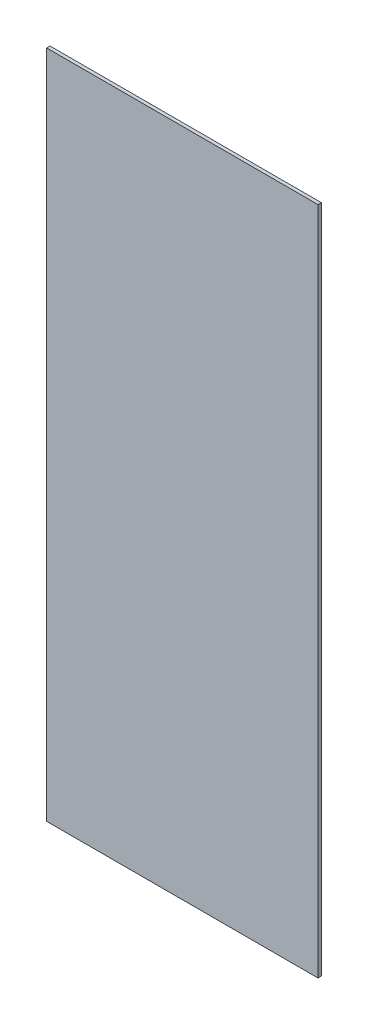
SolidWorks part; units mm, degrees
material "201 Annealed Stainless Steel (SS)"
ref_plane "Front Plane" through (0, 0, 0) normal (0, 0, 1) x (1, 0, 0)
ref_plane "Top Plane" through (0, 0, 0) normal (0, 1, 0) x (1, 0, 0)
ref_plane "Right Plane" through (0, 0, 0) normal (1, 0, 0) x (0, 0, -1)
sketch "Sketch1" plane through (0, 0, 0) normal (0, 0, 1) x (1, 0, 0)
  line L1 (-81, -200) -> (81, -200)
  line L2 (-81, -200) -> (-81, 200)
  line L3 (-81, 200) -> (81, 200)
  line L4 (81, -200) -> (81, 200)
  line L5 (-81, -200) -> (81, 200) construction
  line L6 (-81, 200) -> (81, -200) construction
  point P0 (0, 0)
  dimension "D1" = 162
  dimension "D2" = 400
extrude "Boss-Extrude1" add sketch "Sketch1" along normal blind 2
sketch "Sketch2" plane through (0, 0, 0) normal (0, 0, -1) x (-1, 0, 0)
  line L0 (79, 200) -> (79, -200) construction
  line L1 (-79, 314.7216) -> (-204.3993, 314.7216)
  line L2 (-79, 314.7216) -> (-79, -251.9618)
  line L3 (-79, -251.9618) -> (-204.3993, -251.9618)
  line L4 (-204.3993, 314.7216) -> (-204.3993, -251.9618)
  line L6 (79, 279.3211) -> (244.4765, 279.3211)
  line L7 (79, 279.3211) -> (79, -295.1839)
  line L8 (79, -295.1839) -> (244.4765, -295.1839)
  line L9 (244.4765, 279.3211) -> (244.4765, -295.1839)
  line L10 (-79, -200) -> (-79, -140) construction
  dimension "D1" = 158
extrude "Cut-Extrude1" [suppressed] cut sketch "Sketch2" against normal through all
sketch "Sketch3" [suppressed] plane through (0, 106, 0) normal (-1, 0, 0) x (0, 0, -1)
  line L0 (-2, -94) -> (0, -94) construction
  circle A0 centre (-7, -84) radius 2.5
  point P6 (-2, -94)
  dimension "D3" = 5
  dimension "D1" = 15
  dimension "D2" = 5
surface "Surface-Extrude1" [suppressed] sketch "Sketch3"
sketch "Sketch4" [suppressed] plane through (-81, 0, 0) normal (-1, 0, 0) x (0, 0, 1)
  line L1 (2, 200) -> (0, 200) construction
  line L2 (0, -200) -> (0, 200) construction
  point P0 (7.5, 196)
  dimension "D1" = 4
  dimension "D2" = 7.5
ref_axis "Axis1" [suppressed] through (-81, 196, 7.5) along (1, 0, 0)
sketch "Sketch5" [suppressed] plane through (0, 0, 0) normal (0, 0, -1) x (-1, 0, 0)
  line L0 (49, 80) -> (49, -80) construction
  line L1 (-49, 80) -> (49, 80)
  line L2 (-49, 80) -> (-49, 60.2594)
  line L3 (-49, 60.2594) -> (49, 60.2594)
  line L4 (49, 80) -> (49, 60.2594)
extrude "Cut-Extrude2" [suppressed] cut sketch "Sketch5" against normal blind 3
sketch "Sketch6" [suppressed] plane through (0, 0, 2) normal (0, 0, 1) x (1, 0, 0)
  line L0 (0, 0) -> (103.2002, 0) construction
  line L1 (-40, 80) -> (-40, 108.3319) construction
  line L2 (-40, 80) -> (-27.987, 80) construction
  line L3 (0, 0) -> (0, 138.3235) construction
  line L4 (40, 80) -> (27.987, 80) construction
  line L5 (40, 80) -> (40, 108.3319) construction
  line L6 (40, -80) -> (40, -108.3319) construction
  line L7 (40, -80) -> (27.987, -80) construction
  line L8 (-40, -80) -> (-27.987, -80) construction
  line L9 (-40, -80) -> (-40, -108.3319) construction
  circle A0 centre (-40, 80) radius 4.5
  circle A2 centre (-45.8, 85.8) radius 1.95
  circle A3 centre (-45.8, 74.2) radius 1.95
  circle A4 centre (-34.2, 74.2) radius 1.95
  circle A5 centre (-34.2, 85.8) radius 1.95
  circle A6 centre (34.2, 85.8) radius 1.95
  circle A7 centre (34.2, 74.2) radius 1.95
  circle A8 centre (45.8, 74.2) radius 1.95
  circle A9 centre (45.8, 85.8) radius 1.95
  circle A10 centre (40, 80) radius 4.5
  circle A11 centre (40, -80) radius 4.5
  circle A12 centre (45.8, -85.8) radius 1.95
  circle A13 centre (45.8, -74.2) radius 1.95
  circle A14 centre (34.2, -74.2) radius 1.95
  circle A15 centre (34.2, -85.8) radius 1.95
  circle A16 centre (-34.2, -85.8) radius 1.95
  circle A17 centre (-34.2, -74.2) radius 1.95
  circle A18 centre (-45.8, -74.2) radius 1.95
  circle A19 centre (-45.8, -85.8) radius 1.95
  circle A20 centre (-40, -80) radius 4.5
  circle A21 centre (-40, 80) radius 5.1 construction
  dimension "D1" = 9
  dimension "D3" = 3.9
extrude "Leandut_holes" [suppressed] cut sketch "Sketch6" against normal through all
chamfer "Chamfer1" [suppressed] distance 5 angle 45
sketch "Sketch7" [suppressed] plane through (0, 0, 2) normal (0, 0, 1) x (1, 0, 0)
  line L0 (81, 200) -> (-81, 200) construction
  line L1 (-31, -125) -> (31, -125)
  line L2 (-31, -125) -> (-31, 180)
  line L3 (-31, 180) -> (31, 180)
  line L4 (31, -125) -> (31, 180)
  line L5 (0, 0) -> (0, -66.8576) construction
  line L7 (-81, 200) -> (-81, -200) construction
  point P0 (0, 0)
  dimension "D1" = 20
  dimension "D2" = 50
  dimension "D3" = 62
  dimension "D4" = 125
extrude "Plunger-Window" [suppressed] cut sketch "Sketch7" against normal through all
sketch "Sketch8" [suppressed] plane through (0, 0, 2) normal (0, 0, 1) x (1, 0, 0)
  line L0 (106, 145) -> (56, 145) construction
  line L1 (-56, 125) -> (56, 125)
  line L2 (-56, 125) -> (-56, 145)
  line L3 (-56, 145) -> (56, 145)
  line L4 (56, 125) -> (56, 145)
  line L5 (56, -110) -> (56, 125) construction
extrude "Cut-Extrude3" [suppressed] cut sketch "Sketch8" against normal blind 5
sketch "Sketch9" [suppressed] plane through (0, 0, 0) normal (0, 0, -1) x (-1, 0, 0)
  line L0 (1.1, 0) -> (-1.1, 0) construction
  line L5 (6, -100) -> (-6, -100)
  line L6 (6, -100) -> (6, 100)
  line L7 (6, 100) -> (-6, 100)
  line L8 (-6, -100) -> (-6, 100)
  line L9 (-81, 120) -> (81, 120) construction
  point P0 (0, 0)
  point P8 (0, 100)
  dimension "D1" = 12
  dimension "D2" = 100
  dimension "D3" = 100
  dimension "D4" = 20
extrude "Plunger-cutout" [suppressed] cut sketch "Sketch9" against normal through all and the other way through all
sketch "Sketch10" plane through (0, 0, 0) normal (0, 0, -1) x (-1, 0, 0)
  line L0 (81, -67.5) -> (209.9137, 101.8916) construction
  line L1 (81, 200) -> (81, -200) construction
  line L2 (81, 200) -> (209.9137, 101.8916) construction
  line L3 (81, 200) -> (81, -67.5) construction
  line L4 (-81, 200) -> (81, 200) construction
  line L5 (-81, 200) -> (81, 200) construction
  line L6 (0, 200) -> (0, 262.0874) construction
  line L7 (-81, 200) -> (-81, -67.5)
  line L8 (-81, 200) -> (-209.9137, 101.8916)
  line L9 (-81, -67.5) -> (-209.9137, 101.8916)
  line L10 (81, 200) -> (81, -200) construction
  dimension "D1" = 67.5
  dimension "D2" = 162
  dimension "D3" = 162
  dimension "D4" = 212.8667
  dimension "D5" = 400
extrude "Boss-Extrude3" [suppressed] add sketch "Sketch10" against normal through all
sketch "Sketch11" [suppressed] plane through (0, 0, 2) normal (0, 0, 1) x (1, 0, 0)
  line L0 (81, 217.5) -> (81, -274.1687)
split line "Split Line1" [suppressed]
sketch "Sketch12" [suppressed] plane through (0, 0, 0) normal (0, 0, -1) x (-1, 0, 0)
  line L0 (81, 120) -> (81, -120) construction
  line L4 (106.722, 31) -> (106.722, -31)
  line L5 (174.722, 31) -> (106.722, 31)
  line L6 (174.722, -31) -> (174.722, 31)
  line L7 (106.722, -31) -> (174.722, -31)
  line L8 (81, 31) -> (81, -31)
  line L9 (174.722, 31) -> (81, 31)
  line L10 (174.722, -31) -> (174.722, 31)
  line L11 (81, -31) -> (174.722, -31)
  circle A0 centre (139.72, 0) radius 8
  circle A4 centre (100.7508, -22.5) radius 5 construction
  circle A5 centre (100.7508, 22.5) radius 5 construction
  circle A6 centre (100.7508, -22.5) radius 5
  circle A7 centre (100.7508, 22.5) radius 5
  dimension "D3" = 16
  dimension "D5" = 139.72
  dimension "D1" = 0
extrude "Boss-Extrude4" [suppressed] add sketch "Sketch12" against normal through all
sketch "Sketch13" plane through (0, 0, 0) normal (0, 0, -1) x (-1, 0, 0)
  line L0 (0, 0) -> (-166.9371, 0) construction
  line L1 (108.207, -100) -> (-114.7867, -100)
  line L2 (108.207, -100) -> (108.207, -177.524)
  line L3 (108.207, -177.524) -> (-114.7867, -177.524)
  line L4 (-114.7867, -100) -> (-114.7867, -177.524)
  line L5 (-103.1423, 100) -> (143.0141, 100)
  line L6 (-103.1423, 100) -> (-103.1423, 181.1211)
  line L7 (-103.1423, 181.1211) -> (143.0141, 181.1211)
  line L8 (143.0141, 100) -> (143.0141, 181.1211)
  dimension "D1" = 200
extrude "Cut-Extrude4" [suppressed] cut sketch "Sketch13" against normal through all
